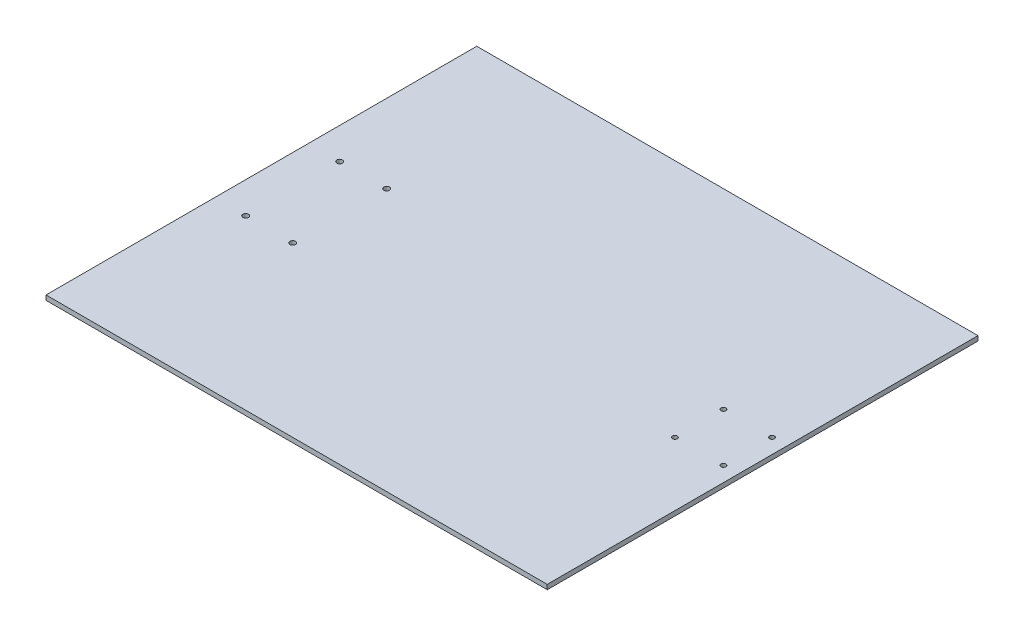
SolidWorks part; units mm, degrees
material "Acrílico (Impacto medio-alto)"
ref_plane "Alzado" through (0, 0, 0) normal (0, 0, 1) x (1, 0, 0)
ref_plane "Planta" through (0, 0, 0) normal (0, 1, 0) x (1, 0, 0)
ref_plane "Vista lateral" through (0, 0, 0) normal (1, 0, 0) x (0, 0, -1)
sketch "Sketch1" plane through (0, 0, 0) normal (0, 1, 0) x (1, 0, 0)
  line L1 (-160, -137.5) -> (160, -137.5)
  line L2 (-160, -137.5) -> (-160, 137.5)
  line L3 (-160, 137.5) -> (160, 137.5)
  line L4 (160, -137.5) -> (160, 137.5)
  line L5 (-160, -137.5) -> (160, 137.5) construction
  line L6 (-160, 137.5) -> (160, -137.5) construction
  point P0 (0, 0)
  dimension "D1" = 320
  dimension "D2" = 275
extrude "Boss-Extrude1" add sketch "Sketch1" along normal blind 3
sketch "Sketch2" plane through (0, 3, 0) normal (0, 1, 0) x (1, 0, 0)
  line L0 (0, 0) -> (160, 0) construction
  line L1 (160, -137.5) -> (160, 137.5) construction
  line L3 (119.5, -15.5) -> (150.5, -15.5)
  line L4 (119.5, -15.5) -> (119.5, 15.5)
  line L5 (119.5, 15.5) -> (150.5, 15.5)
  line L6 (150.5, -15.5) -> (150.5, 15.5)
  line L7 (119.5, -15.5) -> (150.5, 15.5) construction
  line L8 (119.5, 15.5) -> (150.5, -15.5) construction
  point P5 (135, 0)
  dimension "D1" = 31
  dimension "D2" = 31
  dimension "D3" = 25
sketch "Sketch3" plane through (0, 3, 0) normal (0, 1, 0) x (1, 0, 0)
  point P0 (150.5, 15.5)
  point P3 (150.5, -15.5)
  point P6 (119.5, -15.5)
  point P9 (119.5, 15.5)
hole_wizard "Taladro de margen para M2.51" positions "Sketch3" profile "Sketch4" hole size "M2.5" standard "ISO" end condition through all
sketch "Sketch4" plane through (150.5, 3, -15.5) normal (1, 0, 0) x (0, 0, 1)
  line L0 (0, 0) -> (0, 3)
  line L1 (0, 3) -> (1.55, 3)
  line L2 (1.55, 3) -> (1.55, 0)
  line L5 (1.55, 0) -> (0, 0)
  line L11 (0, -6.35) -> (0, 107.95) construction
  dimension "Diámetro de taladro hasta el siguiente" = 3.1
  dimension "Profundidad de taladro hasta el siguiente" = 3
sketch "Sketch5" plane through (0, 3, 0) normal (0, 1, 0) x (1, 0, 0)
  line L0 (0, 0) -> (-160, 0) construction
  line L1 (-160, 137.5) -> (-160, -137.5) construction
  line L3 (-140, -30) -> (-110, -30)
  line L4 (-140, -30) -> (-140, 30)
  line L5 (-140, 30) -> (-110, 30)
  line L6 (-110, -30) -> (-110, 30)
  line L7 (-140, -30) -> (-110, 30) construction
  line L8 (-140, 30) -> (-110, -30) construction
  point P4 (-125, 0)
  dimension "D1" = 35
  dimension "D2" = 60
  dimension "D3" = 30
sketch "Sketch6" plane through (0, 3, 0) normal (0, 1, 0) x (1, 0, 0)
  point P0 (-110, 30)
  point P3 (-110, -30)
  point P6 (-140, -30)
  point P9 (-140, 30)
hole_wizard "Taladro de margen para M32" positions "Sketch6" profile "Sketch7" hole size "M3" standard "ISO" end condition through all
sketch "Sketch7" plane through (-110, 3, -30) normal (1, 0, 0) x (0, 0, 1)
  line L0 (0, 0) -> (0, 3)
  line L1 (0, 3) -> (1.8, 3)
  line L2 (1.8, 3) -> (1.8, 0)
  line L5 (1.8, 0) -> (0, 0)
  line L11 (0, -6.35) -> (0, 107.95) construction
  dimension "Diámetro de taladro hasta el siguiente" = 3.6
  dimension "Profundidad de taladro hasta el siguiente" = 3
